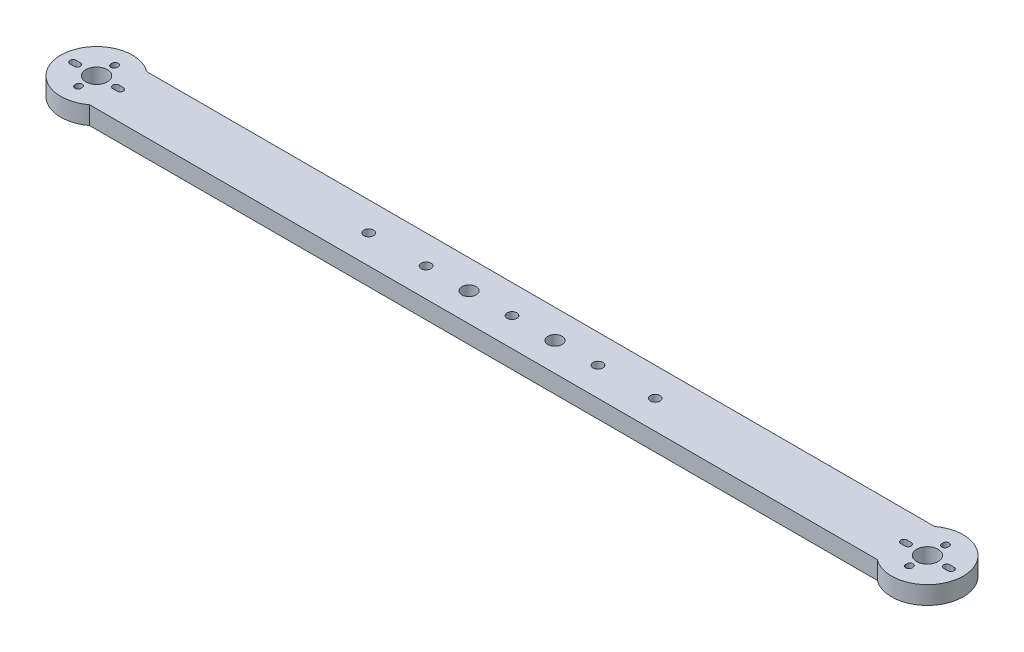
SolidWorks part; units mm, degrees
material "Thornel Mat VMA"
ref_plane "Front Plane" through (0, 0, 0) normal (0, 0, 1) x (1, 0, 0)
ref_plane "Top Plane" through (0, 0, 0) normal (0, 1, 0) x (1, 0, 0)
ref_plane "Right Plane" through (0, 0, 0) normal (1, 0, 0) x (0, 0, -1)
sketch "Sketch1" plane through (0, 0, 0) normal (0, 1, 0) x (1, 0, 0)
  line L0 (0, 12.7) -> (0, -12.7) construction
  line L1 (-174.625, 12.7) -> (174.625, 12.7)
  line L3 (-174.625, -12.7) -> (174.625, -12.7)
  arc A0 (-174.625, 12.7) -> (-174.625, -12.7) centre (-184.15, 0) ccw
  arc A1 (174.625, -12.7) -> (174.625, 12.7) centre (184.15, 0) ccw
  point P8 (0, 12.7)
  point P12 (0, 0)
  dimension "D3" = 31.75
  dimension "D4" = 31.75
extrude "Boss-Extrude1" add sketch "Sketch1" along normal blind 8
sketch "Sketch2" plane through (0, 8, 0) normal (0, 1, 0) x (1, 0, 0)
  line L0 (173.6914, 0) -> (175.6086, 0) construction
  line L1 (173.6914, 1.375) -> (175.6086, 1.375)
  line L2 (173.6914, -1.375) -> (175.6086, -1.375)
  line L3 (184.15, 0) -> (184.15, 3.2374) construction
  line L4 (194.6086, 0) -> (192.6914, 0) construction
  line L5 (194.6086, 1.375) -> (192.6914, 1.375)
  line L6 (194.6086, -1.375) -> (192.6914, -1.375)
  line L7 (184.15, 8.25) -> (184.15, 7.75) construction
  line L8 (185.525, 8.25) -> (185.525, 7.75)
  line L9 (182.775, 8.25) -> (182.775, 7.75)
  line L10 (184.15, -8.25) -> (184.15, -7.75) construction
  line L11 (185.525, -8.25) -> (185.525, -7.75)
  line L12 (182.775, -8.25) -> (182.775, -7.75)
  line L13 (0, 0) -> (184.15, 0) construction
  line L14 (0, 0) -> (0, 12.7) construction
  line L15 (174.625, 12.7) -> (-174.625, 12.7) construction
  line L16 (-184.15, 0) -> (-184.15, 3.2374) construction
  line L17 (-184.15, -8.25) -> (-184.15, -7.75) construction
  line L18 (-185.525, -8.25) -> (-185.525, -7.75)
  line L19 (-182.775, -8.25) -> (-182.775, -7.75)
  line L20 (-184.15, 8.25) -> (-184.15, 7.75) construction
  line L21 (-185.525, 8.25) -> (-185.525, 7.75)
  line L22 (-182.775, 8.25) -> (-182.775, 7.75)
  line L23 (-194.6086, 0) -> (-192.6914, 0) construction
  line L24 (-194.6086, 1.375) -> (-192.6914, 1.375)
  line L25 (-194.6086, -1.375) -> (-192.6914, -1.375)
  line L26 (-173.6914, 0) -> (-175.6086, 0) construction
  line L27 (-173.6914, 1.375) -> (-175.6086, 1.375)
  line L28 (-173.6914, -1.375) -> (-175.6086, -1.375)
  line L29 (184.15, 8) -> (184.15, -8) construction
  circle A0 centre (184.15, 0) radius 4.75
  arc A1 (173.6914, 1.375) -> (173.6914, -1.375) centre (173.6914, 0) ccw
  arc A2 (175.6086, -1.375) -> (175.6086, 1.375) centre (175.6086, 0) ccw
  arc A3 (194.6086, 1.375) -> (194.6086, -1.375) centre (194.6086, 0) cw
  arc A4 (192.6914, -1.375) -> (192.6914, 1.375) centre (192.6914, 0) cw
  arc A5 (185.525, 8.25) -> (182.775, 8.25) centre (184.15, 8.25) ccw
  arc A6 (182.775, 7.75) -> (185.525, 7.75) centre (184.15, 7.75) ccw
  arc A7 (185.525, -8.25) -> (182.775, -8.25) centre (184.15, -8.25) cw
  arc A8 (182.775, -7.75) -> (185.525, -7.75) centre (184.15, -7.75) cw
  circle A9 centre (-184.15, 0) radius 4.75
  arc A10 (-185.525, -8.25) -> (-182.775, -8.25) centre (-184.15, -8.25) ccw
  arc A11 (-182.775, -7.75) -> (-185.525, -7.75) centre (-184.15, -7.75) ccw
  arc A12 (-185.525, 8.25) -> (-182.775, 8.25) centre (-184.15, 8.25) cw
  arc A13 (-182.775, 7.75) -> (-185.525, 7.75) centre (-184.15, 7.75) cw
  arc A14 (-194.6086, 1.375) -> (-194.6086, -1.375) centre (-194.6086, 0) ccw
  arc A15 (-192.6914, -1.375) -> (-192.6914, 1.375) centre (-192.6914, 0) ccw
  arc A16 (-173.6914, 1.375) -> (-173.6914, -1.375) centre (-173.6914, 0) cw
  arc A17 (-175.6086, -1.375) -> (-175.6086, 1.375) centre (-175.6086, 0) cw
  point P4 (174.65, 0)
  point P12 (193.65, 0)
  point P19 (184.15, 8)
  point P26 (184.15, -8)
  point P41 (-184.15, -8)
  point P48 (-184.15, 8)
  point P55 (-193.65, 0)
  point P62 (-174.65, 0)
  point P67 (184.15, 0)
  dimension "D4" = 9.5
  dimension "D1" = 16
  dimension "D2" = 19
  dimension "D3" = 184.15
  dimension "D5" = 0.5
  dimension "D6" = 0.5
extrude "Cut-Extrude1" cut sketch "Sketch2" against normal through all
sketch "Sketch3" plane through (0, 8, 0) normal (0, 1, 0) x (1, 0, 0)
  circle A0 centre (0, 0) radius 2.159
  circle A1 centre (38.1, 0) radius 2.159
  circle A2 centre (-38.1, 0) radius 2.159
  dimension "D1" = 38.1
  dimension "D3" = 4.318
  dimension "D4" = 4.318
  dimension "D5" = 4.318
  dimension "D2" = 38.1
extrude "Cut-Extrude2" cut sketch "Sketch3" against normal through all
sketch "Sketch4" plane through (0, 8, 0) normal (0, 1, 0) x (1, 0, 0)
  circle A0 centre (-19.05, 0) radius 3.175
  circle A1 centre (19.05, 0) radius 3.175
  dimension "D1" = 19.05
  dimension "D2" = 19.05
extrude "Cut-Extrude3" cut sketch "Sketch4" against normal through all
sketch "Sketch5" plane through (0, 8, 0) normal (0, 1, 0) x (1, 0, 0)
  line L0 (0, 12.7) -> (0, -22.99) construction
  line L1 (174.625, 12.7) -> (-174.625, 12.7) construction
  circle A0 centre (63.5, 0) radius 2.159
  circle A1 centre (184.15, 0) radius 4.75 construction
  circle A2 centre (-63.5, 0) radius 2.159
  dimension "D1" = 4.318
  dimension "D2" = 120.65
extrude "Cut-Extrude4" cut sketch "Sketch5" against normal through all
